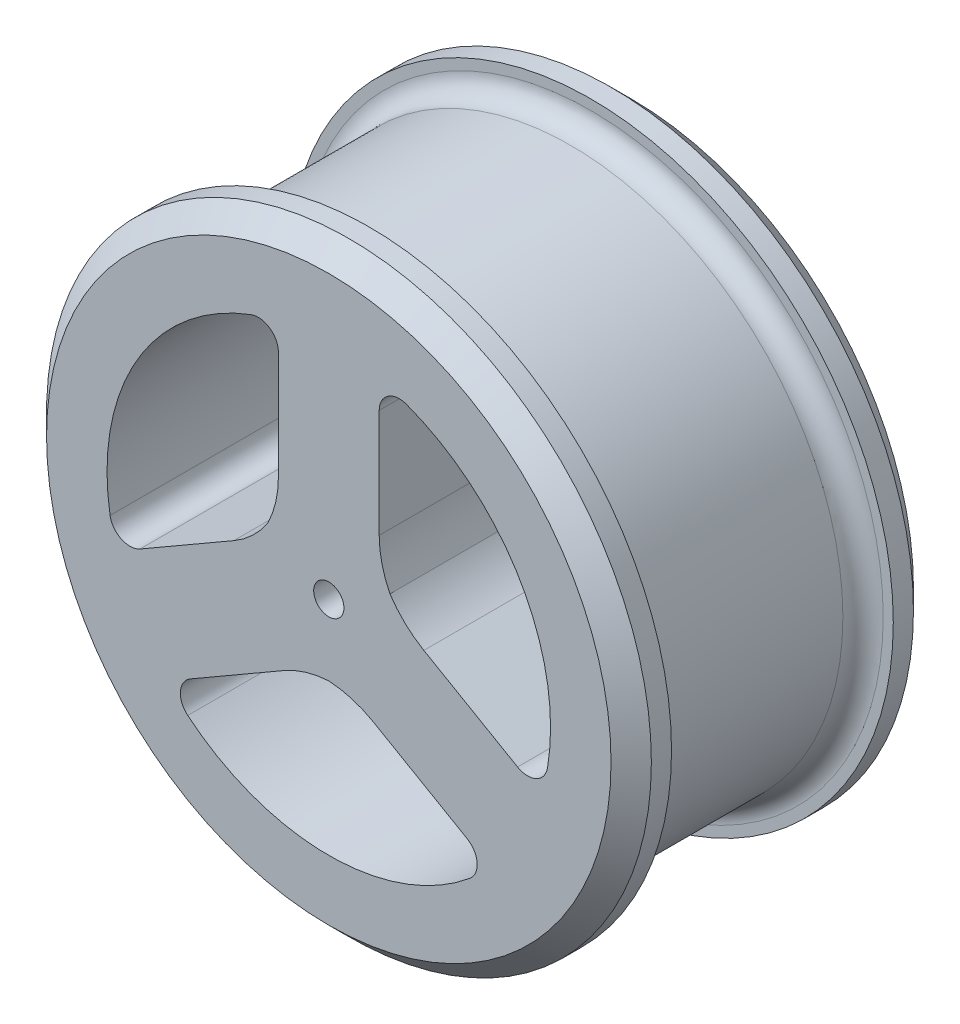
SolidWorks part; units mm, degrees
ref_plane "Front Plane" through (0, 0, 0) normal (0, 0, 1) x (1, 0, 0)
ref_plane "Top Plane" through (0, 0, 0) normal (0, 1, 0) x (1, 0, 0)
ref_plane "Right Plane" through (0, 0, 0) normal (1, 0, 0) x (0, 0, -1)
sketch "Sketch1" plane through (0, 0, 0) normal (0, 0, 1) x (1, 0, 0)
  circle A0 centre (0, 0) radius 15
  circle A1 centre (0, 0) radius 0.75
  dimension "D1" = 30
  dimension "D2" = 1.5
extrude "Boss-Extrude1" add sketch "Sketch1" along normal blind 15
ref_plane "Plane4" through (0, 0, 13) normal (0, 0, 1) x (1, 0, 0)
sketch "Sketch2" plane through (0, 0, 13) normal (0, 0, 1) x (1, 0, 0)
  circle A0 centre (0, 0) radius 13.5
  circle A3 centre (0, 0) radius 15
  circle A4 centre (0, 0) radius 15
  dimension "D1" = 27
  dimension "D2" = 0
extrude "Cut-Extrude1" cut sketch "Sketch2" against normal blind 11
fillet "Fillet1" radius 1 2 edges at (13.5, 0, 13) (13.5, 0, 2)
sketch "Sketch4" plane through (0, 0, 15) normal (0, 0, 1) x (1, 0, 0)
  line L0 (0, 0) -> (0, 15) construction
  line L1 (0, 0) -> (12.9904, -7.5) construction
  line L2 (0, 0) -> (-12.9904, -7.5) construction
  line L3 (2.5, 2.4495) -> (2.5, 10.7121)
  line L4 (-2.5, 2.4495) -> (-2.5, 10.7121)
  line L5 (-2.5, 6.5808) -> (2.5, 6.5808) construction
  line L6 (6.9492, -1.1253) -> (4.4492, -5.4555) construction
  line L7 (0.8713, -3.3898) -> (8.027, -7.5211)
  line L8 (3.3713, 0.9403) -> (10.527, -3.191)
  line L9 (-4.4492, -5.4555) -> (-6.9492, -1.1253) construction
  line L10 (-3.3713, 0.9403) -> (-10.527, -3.191)
  line L11 (-0.8713, -3.3898) -> (-8.027, -7.5211)
  circle A0 centre (0, 0) radius 13.5 construction
  circle A1 centre (0, 0) radius 3.5
  circle A2 centre (0, 0) radius 11
  circle A3 centre (0, 0) radius 15 construction
  point P13 (0, 0)
  point P18 (0, 0)
  point P19 (0, 0)
  point P33 (0, 0)
  dimension "D1" = 27
  dimension "D2" = 7
  dimension "D3" = 22
  dimension "D4" = 3
  dimension "D5" = 5
  dimension "D6" = 3
extrude "Cut-Extrude2" cut sketch "Sketch4" against normal through all contours L8 A2 L3 A1 | L11 A2 L7 A1 | L4 A2 L10 A1 region at (6.5072, 3.7569, 15) region at (-6.5072, 3.7569, 15) region at (0, -7.5139, 15)
fillet "Fillet2" radius 5 6 edges at (-0.8713, -3.3898, 7.5) (0.8713, -3.3898, 7.5) (3.3713, 0.9403, 7.5) (2.5, 2.4495, 7.5) (-3.3713, 0.9403, 7.5) (-2.5, 2.4495, 7.5)
fillet "Fillet3" radius 1 6 edges at (-10.527, -3.191, 7.5) (-8.027, -7.5211, 7.5) (8.027, -7.5211, 7.5) (10.527, -3.191, 7.5) (-2.5, 10.7121, 7.5) (2.5, 10.7121, 7.5)
chamfer "Chamfer2" distance 1 angle 45 2 edges at (15, 0, 0) (15, 0, 15)
